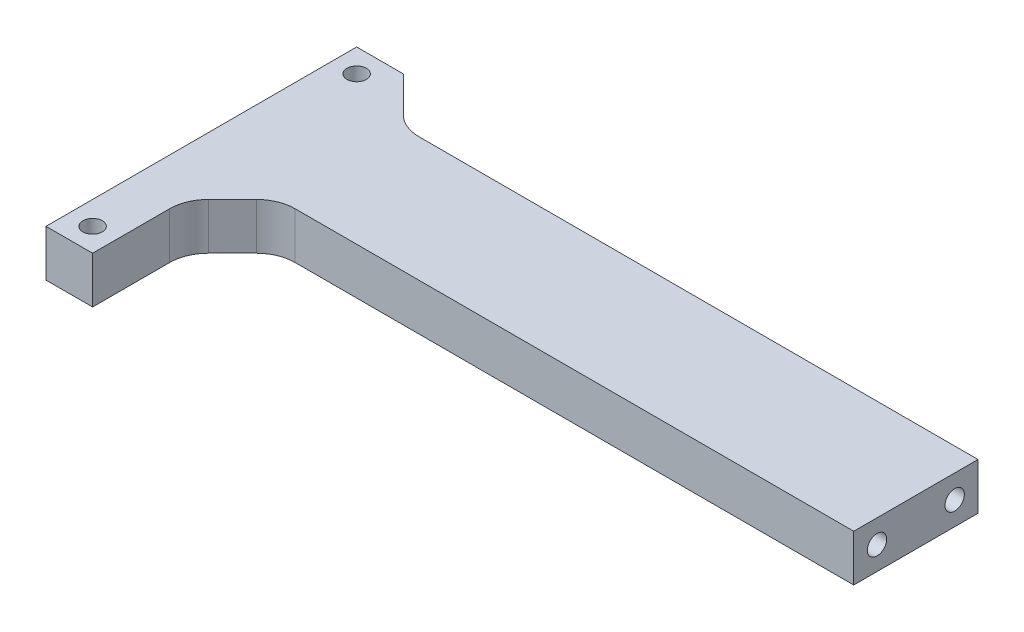
SolidWorks part; units mm, degrees
material "1060 Alloy"
ref_plane "Front Plane" through (0, 0, 0) normal (0, 0, 1) x (1, 0, 0)
ref_plane "Top Plane" through (0, 0, 0) normal (0, 1, 0) x (1, 0, 0)
ref_plane "Right Plane" through (0, 0, 0) normal (1, 0, 0) x (0, 0, -1)
sketch "Sketch2" plane through (0, 0, 0) normal (0, 1, 0) x (1, 0, 0)
  line L0 (6, 0) -> (86, 0)
  line L1 (86, 0) -> (86, -16)
  line L2 (86, -16) -> (6, -16)
  line L3 (6, -16) -> (6, -34)
  line L4 (6, -34) -> (0, -34)
  line L5 (0, -34) -> (0, 0)
  line L6 (0, 0) -> (0, 6)
  line L7 (0, 6) -> (6, 6)
  line L8 (6, 6) -> (6, 0)
  dimension "D1" = 86
  dimension "D2" = 16
  dimension "D3" = 6
  dimension "D4" = 6
  dimension "D5" = 34
  dimension "D6" = 6
extrude "Boss-Extrude1" add sketch "Sketch2" along normal blind 6
hole_wizard "Tap Drill for M3 Tap1" positions "Sketch4" profile "Sketch3" hole size "M3" standard "ISO"
sketch "Sketch4" plane through (0, 0, 0) normal (-1, 0, 0) x (0, 0, 1)
  line L0 (-6, 0) -> (34, 0) construction
  line L1 (0, 6) -> (0, 0) construction
  point P0 (3, 3)
  point P2 (13, 3)
  dimension "D1" = 3
  dimension "D2" = 3
  dimension "D3" = 10
sketch "Sketch3" plane through (0, 3, 3) normal (0, 1, 0) x (0, 0, 1)
  line L0 (0, 0) -> (0, 10.7511)
  line L1 (0, 10.7511) -> (1.25, 10)
  line L2 (1.25, 10) -> (1.25, 0)
  line L5 (1.25, 0) -> (0, 0)
  line L10 (0, 10.7511) -> (-1.25, 10) construction
  line L11 (0, -6.35) -> (0, 107.95) construction
  dimension "Hole Dia." = 2.5
  dimension "Hole Depth" = 10
  dimension "Drill Angle" = 118
hole_wizard "Tap Drill for M3 Tap2" positions "Sketch6" profile "Sketch5" hole size "M3" standard "ISO"
sketch "Sketch6" plane through (86, 0, 0) normal (1, 0, 0) x (0, 0, -1)
  line L0 (0, 6) -> (0, 0) construction
  line L1 (-16, 0) -> (0, 0) construction
  point P0 (-13, 3)
  point P2 (-3, 3)
  dimension "D1" = 3
  dimension "D2" = 3
  dimension "D3" = 10
sketch "Sketch5" plane through (86, 3, 13) normal (0, 1, 0) x (0, 0, -1)
  line L0 (0, 0) -> (0, 10.7511)
  line L1 (0, 10.7511) -> (1.25, 10)
  line L2 (1.25, 10) -> (1.25, 0)
  line L5 (1.25, 0) -> (0, 0)
  line L10 (0, 10.7511) -> (-1.25, 10) construction
  line L11 (0, -6.35) -> (0, 107.95) construction
  dimension "Hole Dia." = 2.5
  dimension "Hole Depth" = 10
  dimension "Drill Angle" = 118
hole_wizard "Tap Drill for M3 Tap3" positions "Sketch8" profile "Sketch7" hole size "M3" standard "ISO"
sketch "Sketch8" plane through (0, 6, 0) normal (0, 1, 0) x (1, 0, 0)
  line L0 (0, 6) -> (0, -34) construction
  line L1 (6, 6) -> (0, 6) construction
  line L2 (0, -34) -> (6, -34) construction
  point P0 (3, 3)
  point P2 (3, -31)
  dimension "D1" = 3
  dimension "D2" = 3
  dimension "D3" = 3
  dimension "D4" = 3
sketch "Sketch7" plane through (3, 6, -3) normal (1, 0, 0) x (0, 0, 1)
  line L0 (0, 0) -> (0, 10.7511)
  line L1 (0, 10.7511) -> (1.25, 10)
  line L2 (1.25, 10) -> (1.25, 0)
  line L5 (1.25, 0) -> (0, 0)
  line L10 (0, 10.7511) -> (-1.25, 10) construction
  line L11 (0, -6.35) -> (0, 107.95) construction
  dimension "Hole Dia." = 2.5
  dimension "Hole Depth" = 10
  dimension "Drill Angle" = 118
chamfer "Chamfer1" distance 6 angle 45 2 edges at (6, 3, 16) (6, 3, 0)
fillet "Fillet1" radius 5 3 edges at (6, 3, 22) (12, 3, 16) (12, 3, 0)
